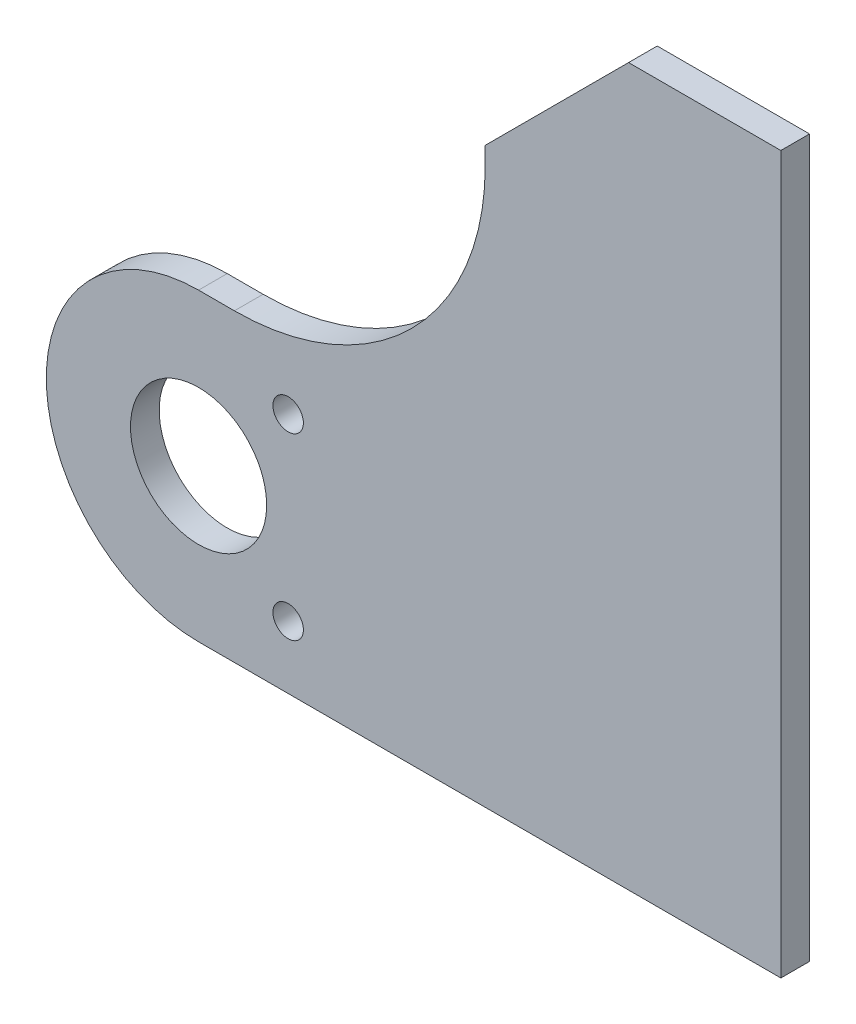
SolidWorks part; units mm, degrees
material "1.0037 (S235JR)"
ref_plane "E_Rechts" through (0, 0, 0) normal (0, 0, 1) x (1, 0, 0)
ref_plane "E_Oben" through (0, 0, 0) normal (0, 1, 0) x (1, 0, 0)
ref_plane "E_Vorne" through (0, 0, 0) normal (1, 0, 0) x (0, 0, -1)
sketch "Skizze1" plane through (0, 0, 0) normal (0, 0, 1) x (1, 0, 0)
  line L0 (0, 42.5) -> (10, 42.5)
  line L1 (80, 112.5) -> (80, 117.5)
  line L2 (120, 157.5) -> (162.5, 157.5)
  line L3 (162.5, 157.5) -> (162.5, -42.5)
  line L4 (162.5, -42.5) -> (0, -42.5)
  line L5 (0, -55) -> (0, 55) construction
  line L6 (80, 117.5) -> (120, 157.5)
  circle A0 centre (0, 0) radius 19
  arc A1 (0, 42.5) -> (0, -42.5) centre (0, 0) ccw
  arc A2 (80, 112.5) -> (10, 42.5) centre (10, 112.5) cw
  point P6 (80, 157.5)
  dimension "D1" = 38
  dimension "D2" = 85
  dimension "D3" = 162.5
  dimension "D4" = 70
  dimension "D5" = 10
  dimension "D6" = 82.5
  dimension "D7" = 200
  dimension "D8" = 162.5
extrude "Aufsatz-Linear austragen1" add sketch "Skizze1" along normal mid plane 8
hole_wizard "M10 Gewindebohrung1" positions "Skizze2" profile "Skizze3" tap size "M10" standard "DIN" end condition through all
sketch "Skizze2" plane through (0, 0, 4) normal (0, 0, 1) x (1, 0, 0)
  line L0 (0, -4.4) -> (0, 4.4) construction
  line L1 (4.4, 0) -> (-4.4, 0) construction
  point P0 (25, -25)
  point P2 (25, 25)
  dimension "D1" = 25
  dimension "D2" = 0
  dimension "D3" = 50
  dimension "D4" = 25
cosmetic thread "Bohrungsgewinde1"
cosmetic thread "Bohrungsgewinde2"
sketch "Skizze3" plane through (25, -25, 4) normal (1, 0, 0) x (0, -1, 0)
  line L0 (0, 0) -> (0, 8)
  line L1 (0, 8) -> (4.25, 8)
  line L2 (4.25, 8) -> (4.25, 0)
  line L5 (4.25, 0) -> (0, 0)
  line L11 (0, -6.35) -> (0, 107.95) construction
  dimension "Bohrerdurchmesser" = 8.5
  dimension "Bohrungstiefe" = 8
